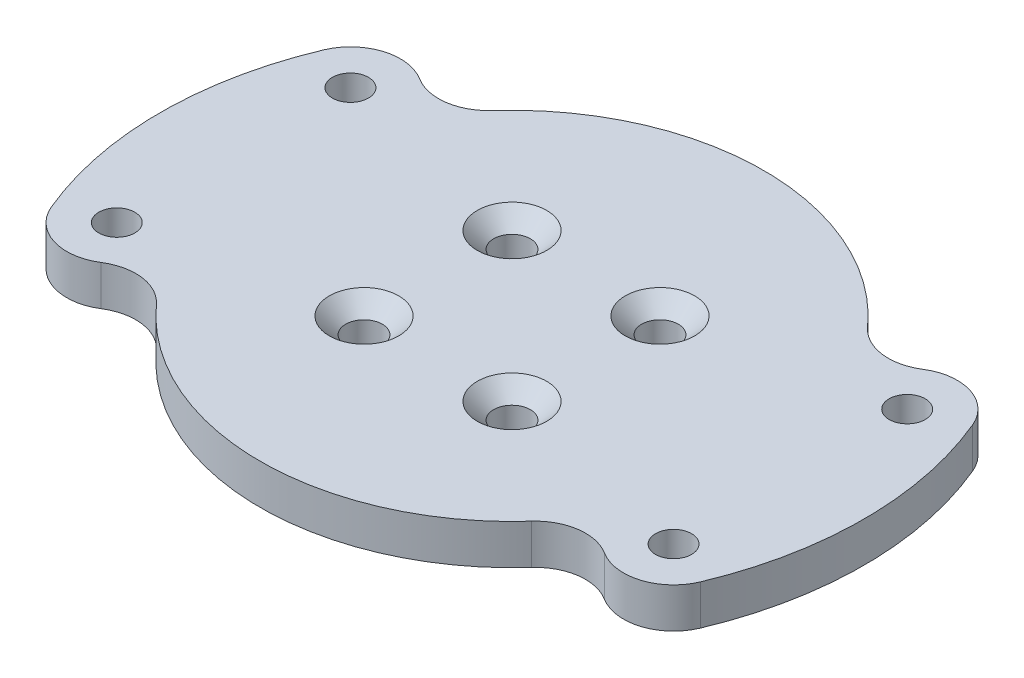
SolidWorks part; units mm, degrees
ref_plane "Front Plane" through (0, 0, 0) normal (0, 0, 1) x (1, 0, 0)
ref_plane "Top Plane" through (0, 0, 0) normal (0, 1, 0) x (1, 0, 0)
ref_plane "Right Plane" through (0, 0, 0) normal (1, 0, 0) x (0, 0, -1)
sketch "Sketch1" plane through (0, 0, 0) normal (0, 1, 0) x (1, 0, 0)
  line L0 (0, 42.5788) -> (0, -44.3324) construction
  line L1 (-11.0839, 11.0839) -> (0, 0) construction
  line L2 (41.7019, 17.5) -> (41.7019, -17.5) construction
  line L3 (31.8836, 20.1646) -> (44.561, 28.1823)
  line L4 (-64.518, 0) -> (71.4295, 0) construction
  line L5 (0, 0) -> (44.561, 28.1823) construction
  line L6 (31.8836, -20.1646) -> (44.561, -28.1823)
  line L7 (-31.8836, -20.1646) -> (-44.561, -28.1823)
  line L8 (-31.8836, 20.1646) -> (-44.561, 28.1823)
  circle A0 centre (0, 0) radius 37.725 construction
  circle A1 centre (-11.0839, 11.0839) radius 2.6
  circle A2 centre (11.0839, 11.0839) radius 2.6
  circle A3 centre (11.0839, -11.0839) radius 2.6
  circle A4 centre (-11.0839, -11.0839) radius 2.6
  circle A9 centre (41.7019, 17.5) radius 2.7
  circle A10 centre (41.7019, -17.5) radius 2.7
  circle A11 centre (0, 0) radius 52.725 construction
  arc A12 (44.561, 28.1823) -> (44.561, -28.1823) centre (0, 0) cw
  arc A13 (-31.8836, 20.1646) -> (31.8836, 20.1646) centre (0, 0) cw
  arc A14 (-31.8836, -20.1646) -> (31.8836, -20.1646) centre (0, 0) ccw
  circle A15 centre (-41.7019, 17.5) radius 2.7
  circle A16 centre (-41.7019, -17.5) radius 2.7
  arc A17 (-44.561, 28.1823) -> (-44.561, -28.1823) centre (0, 0) ccw
  point P18 (0, 0)
  point P23 (0, 0)
  point P27 (41.7019, 0)
  dimension "D1" = 75.45
  dimension "D3" = 5.2
  dimension "D6" = 15
  dimension "D9" = 5.4
  dimension "D2" = 15.675
  dimension "D4" = 45
  dimension "D7" = 45.225
  dimension "D8" = 35
  dimension "D10" = 7.5
  dimension "D5" = 4
extrude "Boss-Extrude1" add sketch "Sketch1" along normal blind 6
fillet "Fillet1" radius 7.5 8 edges at (44.561, 3, 28.1823) (31.8836, 3, 20.1646) (-44.561, 3, 28.1823) (-31.8836, 3, 20.1646) (44.561, 3, -28.1823) (31.8836, 3, -20.1646) (-44.561, 3, -28.1823) (-31.8836, 3, -20.1646)
hole_wizard "CSK for M5 Flat Head Machine Screw1" positions "Sketch5" profile "Sketch4" countersink size "M5" standard "ANSI Metric" end condition through all
sketch "Sketch5" plane through (0, 6, 0) normal (0, 1, 0) x (1, 0, 0)
  point P0 (-11.0839, 11.0839)
  point P3 (11.0839, 11.0839)
  point P6 (11.0839, -11.0839)
  point P9 (-11.0839, -11.0839)
sketch "Sketch4" plane through (-11.0839, 6, -11.0839) normal (1, 0, 0) x (0, 0, 1)
  line L0 (0, 0) -> (0, 6)
  line L1 (0, 6) -> (2.75, 6)
  line L2 (2.75, 6) -> (2.75, 2.45)
  line L3 (2.75, 2.45) -> (5.2, 0)
  line L5 (5.2, 0) -> (0, 0)
  line L6 (-2.75, 2.45) -> (-5.2, 0) construction
  line L11 (0, -6.35) -> (0, 107.95) construction
  dimension "Thru Hole Dia." = 5.5
  dimension "Thru Hole Depth" = 6
  dimension "Near C'Sink Dia." = 10.4
  dimension "Near C'Sink Angle" = 90
equation "\"D7@Sketch1\"=\"D1@Sketch1\"/2+\"D6@Sketch1\"/2"
